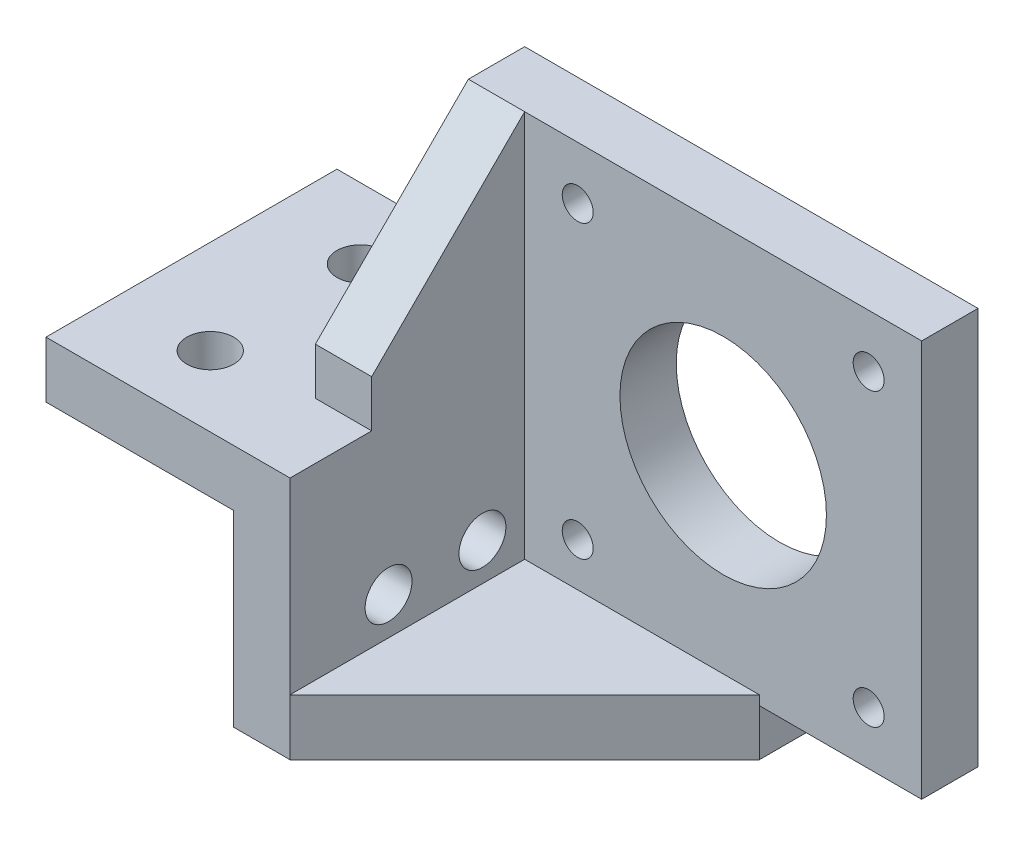
SolidWorks part; units mm, degrees
ref_plane "Front Plane" through (0, 0, 0) normal (1, 0, 0) x (0, 1, 0)
ref_plane "Top Plane" through (0, 0, 0) normal (0, 0, 1) x (0, 1, 0)
ref_plane "Right Plane" through (0, 0, 0) normal (0, 1, 0) x (-1, 0, 0)
sketch "Sketch2" plane through (0, 0, 0) normal (0, 0, 1) x (0, 1, 0)
  line L1 (0, 0) -> (20, 0)
  line L2 (0, 0) -> (0, -20)
  line L3 (0, -20) -> (20, -20)
  line L4 (20, 0) -> (20, -20)
  line L5 (0, 0) -> (26, 0)
  line L6 (0, 0) -> (0, -26)
  line L7 (0, -26) -> (26, -26)
  line L8 (26, 0) -> (26, -26)
  dimension "D1" = 20
  dimension "D2" = 20
  dimension "D3" = 6
  dimension "D4" = 6
extrude "Boss-Extrude3" add sketch "Sketch2" along normal blind 31 separate body contours L8 L5 L4 L3 L6 L7 region at (0.3677, 23, 0)
sketch "Sketch3" plane through (0, 0, 0) normal (0, 0, -1) x (1, 0, 0)
  line L0 (26, 0) -> (26, -26) construction
  line L1 (26, -5) -> (68.3, -5)
  line L2 (26, -5) -> (26, -47.3)
  line L3 (26, -47.3) -> (68.3, -47.3)
  line L4 (68.3, -5) -> (68.3, -47.3)
  line L5 (47.15, -47.3) -> (47.15, -5) construction
  line L6 (26, -26.15) -> (68.3, -26.15) construction
  line L7 (20, 0) -> (26, 0) construction
  line L8 (62.65, -41.65) -> (31.65, -41.65) construction
  line L9 (62.65, -41.65) -> (62.65, -10.65) construction
  line L10 (62.65, -10.65) -> (31.65, -10.65) construction
  line L11 (31.65, -41.65) -> (31.65, -10.65) construction
  line L12 (62.65, -41.65) -> (31.65, -10.65) construction
  line L13 (62.65, -10.65) -> (31.65, -41.65) construction
  circle A0 centre (47.15, -26.15) radius 11
  circle A1 centre (31.65, -10.65) radius 1.65
  circle A2 centre (62.65, -10.65) radius 1.65
  circle A3 centre (62.65, -41.65) radius 1.65
  circle A4 centre (31.65, -41.65) radius 1.65
  point P240 (47.15, -26.15)
  line M9 (26, -26) -> (26, 0)
  dimension "D2" = 3.3
  dimension "D3" = 22
  dimension "D1" = 42.3
  dimension "D4" = 31
  dimension "D5" = 5
extrude "Boss-Extrude4" add sketch "Sketch3" against normal blind 6 contours L4 L1 L2 L3 A4 A3 A2 A1 A0 M9 region at (47.15, 5.5982, 0)
sketch "Sketch4" plane through (0, 20, 0) normal (0, -1, 0) x (1, 0, 0)
  line L0 (10, 31) -> (10, 0) construction
  line L1 (0, 31) -> (20, 31) construction
  line L2 (0, 0) -> (20, 0) construction
  line L3 (20, 15.5) -> (0, 15.5) construction
  line L4 (20, 31) -> (20, 0) construction
  line L5 (0, 31) -> (0, 0) construction
  circle A0 centre (10, 7.5) radius 2.5
  circle A1 centre (10, 23.5) radius 2.5
  point P10 (10, 15.5)
  dimension "D1" = 5
  dimension "D2" = 8
  dimension "D3" = 8
extrude "Cut-Extrude1" cut sketch "Sketch4" against normal up to surface (6 mm away) up to face at (15.6, 26, 13.6)
sketch "Sketch7" plane through (20, 0, 0) normal (-1, 0, 0) x (0, -1, 0)
  line L0 (-10, 31) -> (-10, 0) construction
  line L1 (0, 31) -> (-20, 31) construction
  line L2 (0, 0) -> (-20, 0) construction
  line L3 (-20, 15.5) -> (0, 15.5) construction
  line L4 (-20, 31) -> (-20, 0) construction
  line L5 (0, 31) -> (0, 0) construction
  circle A0 centre (-10, 20.5) radius 2.5
  circle A1 centre (-10, 10.5) radius 2.5
  point P17 (-10, 15.5)
  dimension "D1" = 5
  dimension "D2" = 5
  dimension "D3" = 5
extrude "Cut-Extrude2" cut sketch "Sketch7" against normal through all contours A0 | A1 region at (20, 10, 20.5) region at (20, 10, 10.5)
sketch "Sketch10" plane through (26, 0, 0) normal (-1, 0, 0) x (0, -1, 0)
  line L0 (-26, 0) -> (-47.3, 0)
  line L1 (-47.3, 0) -> (-47.3, 6)
  line L2 (-47.3, 6) -> (-26, 6)
  line L3 (-26, 6) -> (-26, 0)
  line L4 (-26, 0) -> (-26, 22.3)
  line L5 (-26, 22.3) -> (-31, 22.3)
  line L6 (-31, 22.3) -> (-47.3, 6)
  line M3 (-26, 0) -> (-26, 6)
  line M4 (-26, 6) -> (-47.3, 6)
  line M5 (-47.3, 6) -> (-47.3, 0)
  line M6 (-47.3, 0) -> (-26, 0)
  dimension "D1" = 45
  dimension "D2" = 5
extrude "Boss-Extrude6" add sketch "Sketch10" along normal blind 6 contours M6 M3 M4 M5 | L5 L6 L4 M4 region at (26, 36.65, 3) region at (26, 33.4169, 12.4663)
sketch "Sketch11" plane through (0, 5, 0) normal (0, -1, 0) x (1, 0, 0)
  line L0 (26, 6) -> (26, 0)
  line L1 (26, 6) -> (26, 0) construction
  line L2 (26, 0) -> (68.3, 0)
  line L3 (68.3, 0) -> (68.3, 6)
  line L4 (68.3, 6) -> (26, 6)
  line L5 (26, 0) -> (26, 31)
  line L6 (26, 31) -> (51, 6)
  line L7 (51, 6) -> (51, 0)
  line M6 (26, 0) -> (68.3, 0)
  line M9 (26, 6) -> (26, 0)
  dimension "D1" = 45
extrude "Boss-Extrude7" add sketch "Sketch11" along normal blind 5 contours L6 L5 L4 | L7 L4 M9 M6 region at (38.5, 5, 3) region at (34.3333, 5, 14.3333)
sketch "Sketch13" plane through (0, 5, 0) normal (0, 1, 0) x (-1, 0, 0)
  line L0 (-51, 6) -> (-26, 31)
  line L1 (-26, 31) -> (-26, 6)
  line L2 (-26, 6) -> (-51, 6)
extrude "Boss-Extrude8" add sketch "Sketch13" along normal blind 1
equation "\"extrusion_width\"= 20mm"
equation "\"frame_height\"= 360mm"
equation "\"frame_width\"= 320mm"
equation "\"frame_length\"= 320mm"
equation "\"bed_radius\"= 100mm"
equation "\"D1@Sketch2\"=\"extrusion_width\""
equation "\"D2@Sketch2\"=\"extrusion_width\""
equation "\"D4@Sketch2\"=\"D3@Sketch2\""
equation "\"D3@Sketch4\"=\"D2@Sketch4\""
equation "\"hole_for_extrusion_mounting\"= 5mm"
equation "\"D2@Sketch7\"=\"hole_for_extrusion_mounting\""
equation "\"D3@Sketch7\"=\"D1@Sketch7\""
equation "\"cantilever_support_thickness\"= 5mm"
equation "\"D5@Sketch3\"=\"cantilever_support_thickness\""
equation "\"D1@Boss-Extrude7\"=\"cantilever_support_thickness\""
equation "\"D1@Sketch4\"=\"hole_for_extrusion_mounting\""
